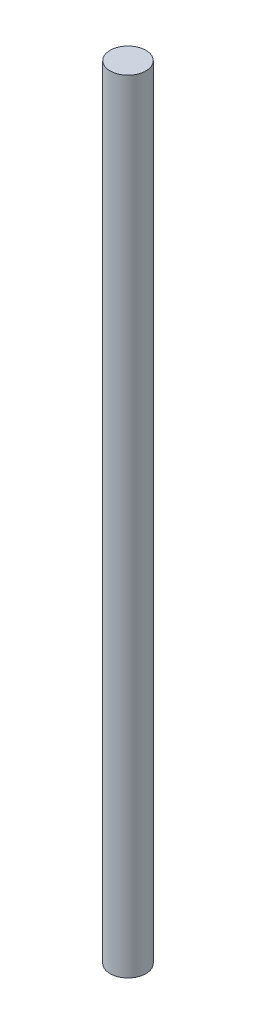
SolidWorks part; units mm, degrees
ref_plane "Front Plane" through (0, 0, 0) normal (0, 0, 1) x (1, 0, 0)
ref_plane "Top Plane" through (0, 0, 0) normal (0, 1, 0) x (1, 0, 0)
ref_plane "Right Plane" through (0, 0, 0) normal (1, 0, 0) x (0, 0, -1)
sketch "Sketch1" plane through (0, 0, 0) normal (0, 1, 0) x (1, 0, 0)
  circle A0 centre (0, 0) radius 2
  dimension "D1" = 4
extrude "Boss-Extrude1" add sketch "Sketch1" along normal blind 87.5
